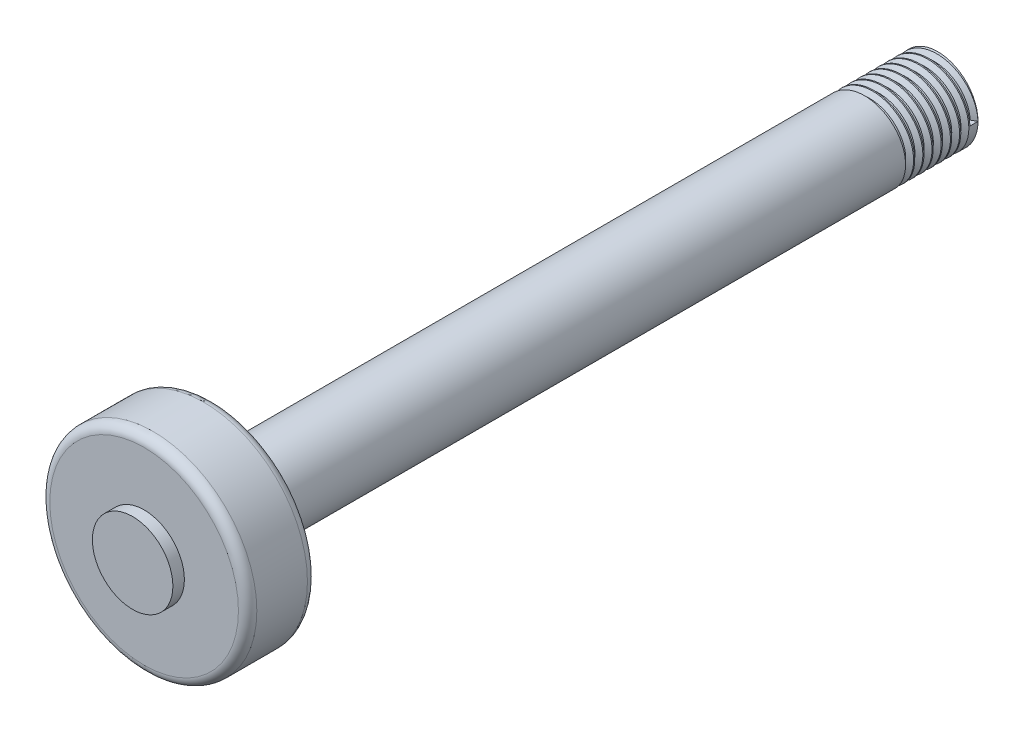
SolidWorks part; units mm, degrees
material "Plain Carbon Steel"
ref_plane "Front Plane" through (0, 0, 0) normal (0, 0, 1) x (1, 0, 0)
ref_plane "Top Plane" through (0, 0, 0) normal (0, 1, 0) x (1, 0, 0)
ref_plane "Right Plane" through (0, 0, 0) normal (1, 0, 0) x (0, 0, -1)
sketch "Sketch1" plane through (0, 0, 0) normal (0, 0, 1) x (1, 0, 0)
  circle A0 centre (0, 0) radius 17.5
  dimension "D1" = 35
extrude "Boss-Extrude1" add sketch "Sketch1" along normal blind 350
thread "Thread1" pitch 4 method cut profile "Thread Profile1" start angle 0, offset 0, length 30, pitch 4, diameter 35
ref_plane "Plane1" through (17.5, 0, 0) normal (0, -1, 0) x (1, 0, 0)
sketch "Thread Profile1" plane through (17.5, 0, 0) normal (0, -1, 0) x (1, 0, 0)
  line L0 (0, 0) -> (0, 4) construction
  line L11 (0, 0) -> (0, 3.5)
  line L12 (0, 3.5) -> (-2.1651, 2.25)
  line L13 (-2.1651, 2.25) -> (-2.1651, 1.25)
  line L15 (-2.1651, 1.25) -> (0, 0)
  line L17 (-2.1651, 1.75) -> (0, 1.75) construction
  point P2 (0, 0)
  dimension "Pitch" = 4
  dimension "Profile_Angle" = 60
  dimension "Profile_Land" = 1
  dimension "Profile_Height" = 2.1651
sketch "Sketch8" plane through (0, 0, 350) normal (0, 0, 1) x (1, 0, 0)
  circle A0 centre (0, 0) radius 45
  circle A1 centre (0, 0) radius 17.5
  circle A2 centre (0, 0) radius 17.5 construction
  circle M3 centre (0, 0) radius 17.5
  dimension "D1" = 90
extrude "Boss-Extrude2" add sketch "Sketch8" against normal blind 30 from offset 5 separate body contours A0 M3 | A0 region at (-43.7272, 0, 350) offset against normal yes
fillet "Fillet1" radius 4 2 edges at (45, 0, 315) (45, 0, 345)
